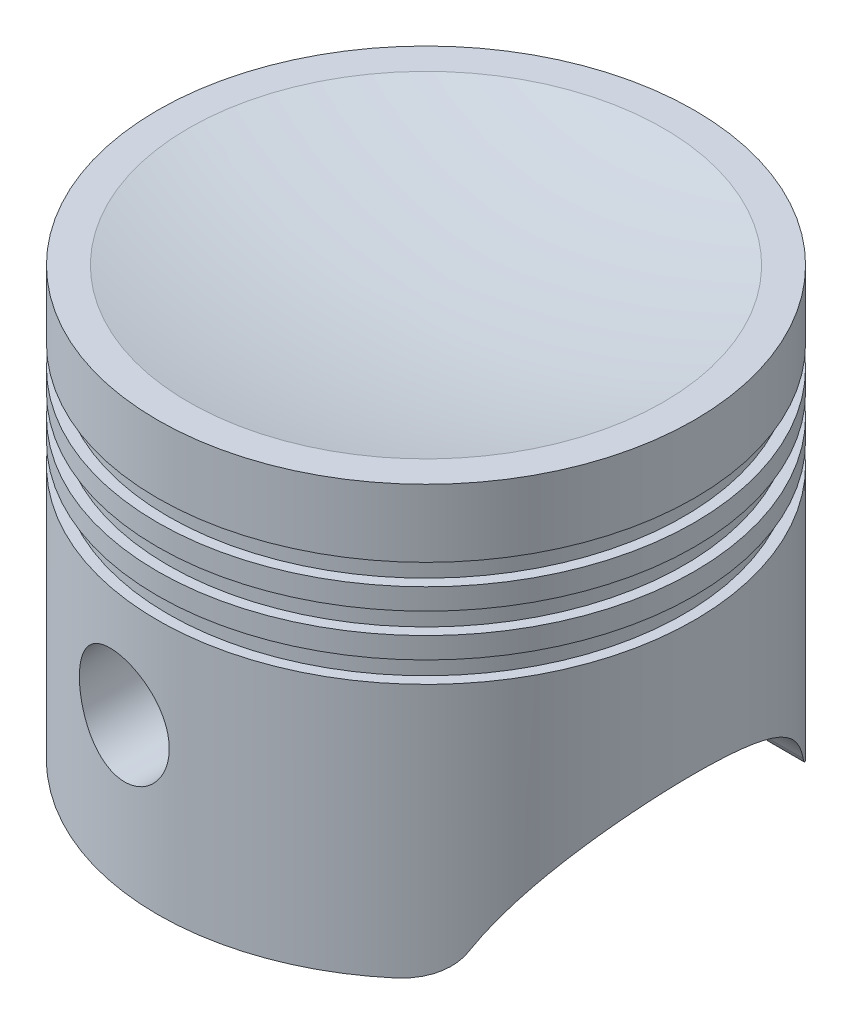
SolidWorks part; units mm, degrees
ref_plane "Front Plane" through (0, 0, 0) normal (0, 0, 1) x (1, 0, 0)
ref_plane "Top Plane" through (0, 0, 0) normal (0, 1, 0) x (1, 0, 0)
ref_plane "Right Plane" through (0, 0, 0) normal (1, 0, 0) x (0, 0, -1)
sketch "Sketch1" plane through (0, 0, 0) normal (0, 0, 1) x (1, 0, 0)
  line L0 (0, 19) -> (0, 0)
  line L1 (0, 0) -> (57.15, 0)
  line L2 (57.15, 0) -> (57.15, -75.3)
  line L3 (57.15, -75.3) -> (63.5, -75.3)
  line L4 (63.5, -75.3) -> (63.5, 26)
  line L5 (63.5, 26) -> (56.15, 26)
  arc A1 (0, 19) -> (56.15, 26) centre (-1.981, 263.592) ccw
  dimension "D7" = 244.6
  dimension "D1" = 19
  dimension "D2" = 101.3
  dimension "D3" = 6.35
  dimension "D4" = 7.35
  dimension "D5" = 63.5
  dimension "D6" = 7
revolve "Revolve1" add sketch "Sketch1" angle 360 about L0
sketch "Sketch2" plane through (0, 0, 0) normal (0, 0, 1) x (1, 0, 0)
  line L0 (63.5, -75.3) -> (63.5, 26) construction
  line L1 (61, 10) -> (63.5, 10)
  line L2 (61, 10) -> (61, 5)
  line L3 (61, 5) -> (63.5, 5)
  line L4 (63.5, 10) -> (63.5, 5)
  line L5 (0, 0) -> (0, 50.0646) construction
  dimension "D1" = 5
  dimension "D2" = 2.5
  dimension "D3" = 5
revolve "Cut-Revolve1" cut sketch "Sketch2" angle 360 about L5
pattern_linear "LPattern1" count 3 spacing 10 along (0, -1, 0) of "Cut-Revolve1"
sketch "Sketch3" plane through (0, 0, 0) normal (0, 0, 1) x (1, 0, 0)
  circle A0 centre (-10, -40) radius 12.7
  point P2 (0, 0)
  point P4 (0, 0)
  point P5 (4.4756, -39.7488)
  point P6 (0, 0)
  dimension "D1" = 25.4
  dimension "D2" = 10
  dimension "D3" = 40
extrude "Cut-Extrude1" cut sketch "Sketch3" against normal through all both and the other way through all
sketch "Sketch4" plane through (0, 0, 0) normal (1, 0, 0) x (0, 0, -1)
  line L0 (-63.5, -75.3) -> (63.5, -75.3) construction
  arc A0 (-42, -75.3) -> (42, -75.3) centre (0, -91.4555) cw
  point P7 (0, -46.4555)
  dimension "D2" = 45
  dimension "D1" = 42
extrude "Cut-Extrude3" cut sketch "Sketch4" against normal through all and the other way through all flip side to cut
fillet "Fillet1" radius 10 4 edges at (43.1917, -75.3, -42) (-43.1917, -75.3, -42) (43.1917, -75.3, 42) (-43.1917, -75.3, 42)
sketch "Sketch5" plane through (0, 0, 0) normal (0, 0, 1) x (1, 0, 0)
  circle A0 centre (-10, -40) radius 12.7 construction
  circle A1 centre (-10, -40) radius 12.7
  circle A2 centre (-10, -40) radius 15.2
  dimension "D1" = 2.5
extrude "Boss-Extrude1" add sketch "Sketch5" along normal up to surface (33.4426 mm away) from offset 30 up to face at (-18.496, -49.4397, -60.7466)
mirror "Mirror1" about plane through (0, 0, 0) normal (0, 0, 1) of "Boss-Extrude1"
